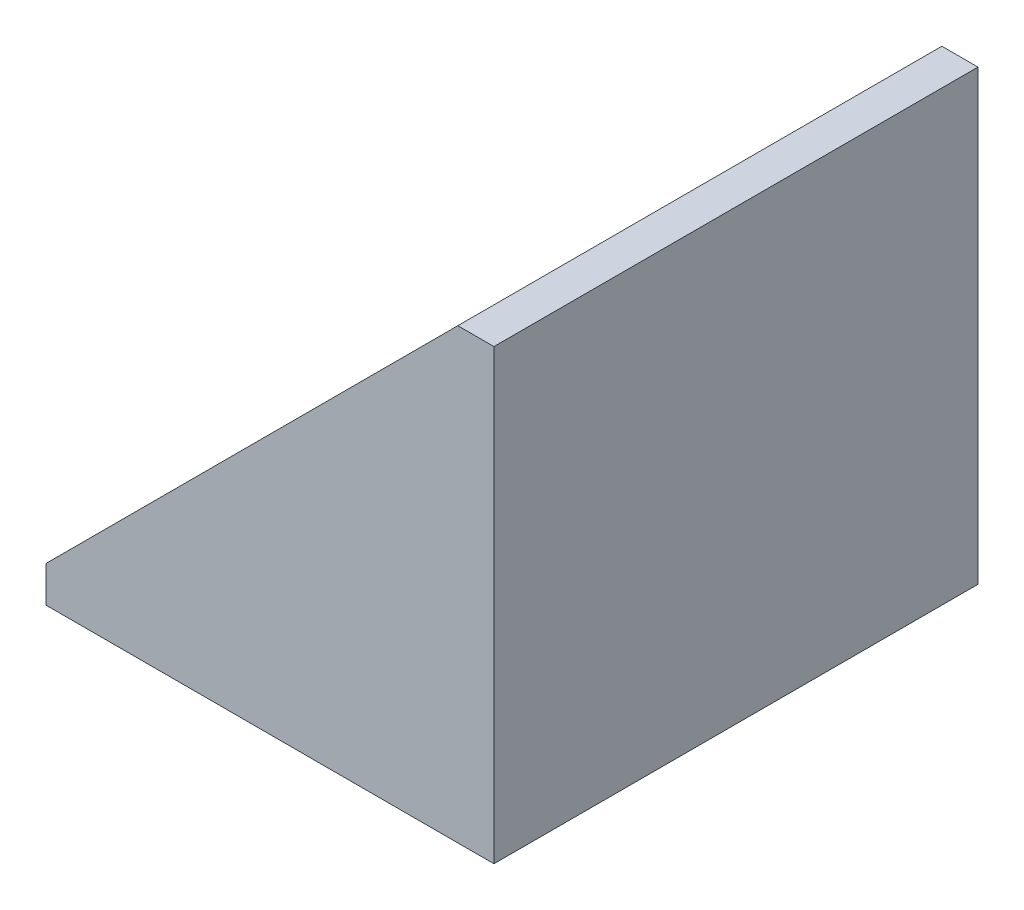
SolidWorks part; units mm, degrees
ref_plane "Front Plane" through (0, 0, 0) normal (0, 0, 1) x (1, 0, 0)
ref_plane "Top Plane" through (0, 0, 0) normal (0, 1, 0) x (1, 0, 0)
ref_plane "Right Plane" through (0, 0, 0) normal (1, 0, 0) x (0, 0, -1)
sketch "Sketch1" plane through (0, 0, 0) normal (0, 1, 0) x (1, 0, 0)
  line L1 (-23.55, -23.55) -> (23.55, -23.55) construction
  line L2 (-23.55, -23.55) -> (-23.55, 23.55) construction
  line L3 (-23.55, 23.55) -> (23.55, 23.55) construction
  line L4 (23.55, -23.55) -> (23.55, 23.55) construction
  line L5 (-23.55, -23.55) -> (23.55, 23.55) construction
  line L6 (-23.55, 23.55) -> (23.55, -23.55) construction
  line L7 (-28.5, -28.5) -> (28.5, -28.5)
  line L8 (-28.5, -28.5) -> (-28.5, 28.5)
  line L9 (-28.5, 28.5) -> (28.5, 28.5)
  line L10 (28.5, -28.5) -> (28.5, 28.5)
  line L11 (-28.5, -28.5) -> (28.5, 28.5) construction
  line L12 (-28.5, 28.5) -> (28.5, -28.5) construction
  circle A0 centre (-23.55, 23.55) radius 2.5
  circle A1 centre (23.55, 23.55) radius 2.5
  circle A2 centre (23.55, -23.55) radius 2.5
  circle A3 centre (-23.55, -23.55) radius 2.5
  circle A4 centre (0, 0) radius 19.2
  point P0 (0, 0)
  point P6 (0, 0)
  point P21 (0, 0)
  dimension "D5" = 5
  dimension "D7" = 38.4
  dimension "D1" = 47.1
  dimension "D2" = 47.1
  dimension "D3" = 57
  dimension "D4" = 57
  dimension "D6" = 4
extrude "Boss-Extrude1" add sketch "Sketch1" along normal blind 5
sketch "Sketch2" plane through (0, 0, 28.5) normal (0, 0, 1) x (1, 0, 0)
  line L1 (28.5, 62) -> (33.5, 62)
  line L2 (28.5, 62) -> (28.5, 0)
  line L3 (28.5, 0) -> (33.5, 0)
  line L4 (33.5, 62) -> (33.5, 0)
  point P5 (0, 0)
  point P6 (28.5, 0)
  dimension "D1" = 5
  dimension "D2" = 62
extrude "Boss-Extrude2" add sketch "Sketch2" against normal up to surface (57 mm away) up to face at (0, 2.5, -28.5)
sketch "Sketch3" plane through (0, 0, 28.5) normal (0, 0, 1) x (1, 0, 0)
  line L0 (28.5, 62) -> (-28.5, 5)
  line L1 (-28.5, 5) -> (-28.5, 0)
  line L2 (-28.5, 0) -> (33.5, 0)
  line L3 (33.5, 0) -> (33.5, 62)
  line L4 (33.5, 62) -> (28.5, 62)
extrude "Boss-Extrude3" add sketch "Sketch3" along normal blind 5
extrude "Boss-Extrude4" add sketch "Sketch3<2>" against normal blind 5 from offset 57 offset against normal yes
sketch "Sketch3<2>" plane through (0, 0, 28.5) normal (0, 0, 1) x (1, 0, 0) same geometry as "Sketch3"
